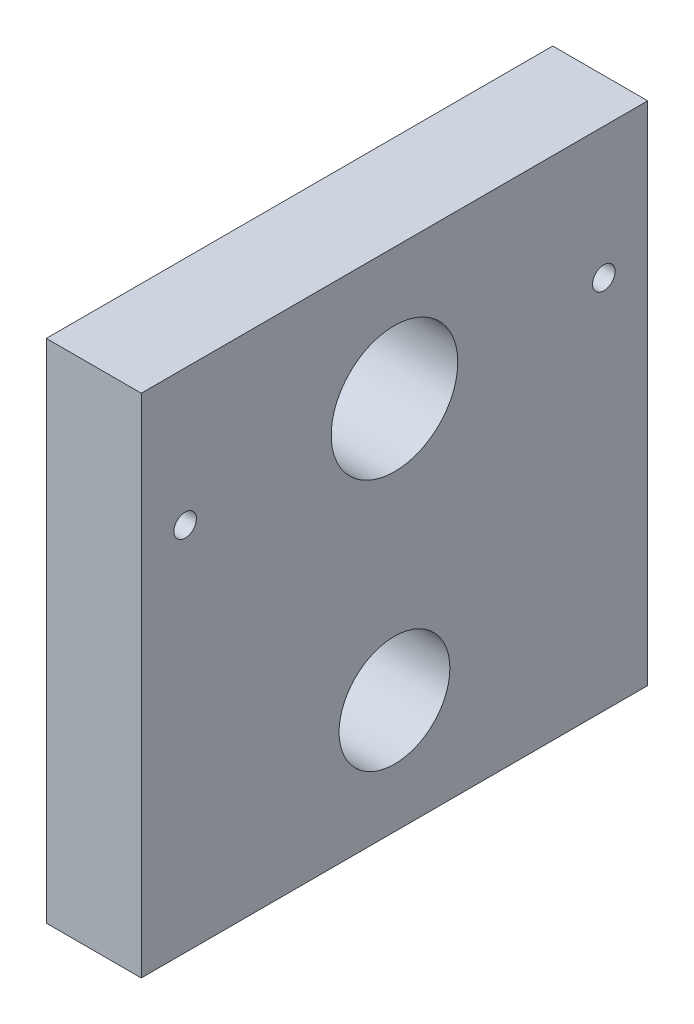
SolidWorks part; units mm, degrees
ref_plane "Front Plane" through (0, 0, 0) normal (0, 0, 1) x (1, 0, 0)
ref_plane "Top Plane" through (0, 0, 0) normal (0, 1, 0) x (1, 0, 0)
ref_plane "Right Plane" through (0, 0, 0) normal (1, 0, 0) x (0, 0, -1)
sketch "Sketch1" plane through (0, 0, 0) normal (1, 0, 0) x (0, 0, -1)
  line L1 (-25.4, -25.4) -> (25.4, -25.4)
  line L2 (-25.4, -25.4) -> (-25.4, 25.4)
  line L3 (-25.4, 25.4) -> (25.4, 25.4)
  line L4 (25.4, -25.4) -> (25.4, 25.4)
  line L5 (-25.4, -25.4) -> (25.4, 25.4) construction
  line L6 (-25.4, 25.4) -> (25.4, -25.4) construction
  point P0 (0, 0)
  dimension "D1" = 50.8
  dimension "D2" = 50.8
extrude "Boss-Extrude1" add sketch "Sketch1" along normal blind 9.525
hole_wizard "7/16 (0.4375) Diameter Hole1" positions "Sketch9" profile "Sketch8" hole size "7/16" standard "ANSI Inch"
sketch "Sketch9" plane through (9.525, 0, 0) normal (1, 0, 0) x (0, 0, -1)
  line L0 (-25.4, -25.4) -> (25.4, -25.4) construction
  point P0 (0, -13.97)
  dimension "D1" = 11.43
sketch "Sketch8" plane through (9.525, -13.97, 0) normal (0, 1, 0) x (0, 0, -1)
  line L0 (0, 0) -> (0, 73.4425)
  line L1 (0, 73.4425) -> (5.5562, 70.104)
  line L2 (5.5562, 70.104) -> (5.5562, 0)
  line L5 (5.5562, 0) -> (0, 0)
  line L10 (0, 73.4425) -> (-5.5563, 70.104) construction
  line L11 (0, -6.35) -> (0, 107.95) construction
  dimension "Hole Dia." = 11.1125
  dimension "Hole Depth" = 70.104
  dimension "Drill Angle" = 118
hole_wizard "1/2 (0.5) Diameter Hole2" positions "Sketch3" profile "Sketch2" hole size "1/2" standard "ANSI Inch"
sketch "Sketch3" plane through (9.525, 0, 0) normal (1, 0, 0) x (0, 0, -1)
  circle A0 centre (0, -13.97) radius 5.5562 construction
  point P0 (0, 12.2301)
  dimension "D1" = 26.2001
  dimension "D2" = 0
sketch "Sketch2" plane through (9.525, 12.2301, 0) normal (0, 1, 0) x (0, 0, -1)
  line L0 (0, 0) -> (0, 73.9195)
  line L1 (0, 73.9195) -> (6.35, 70.104)
  line L2 (6.35, 70.104) -> (6.35, 0)
  line L5 (6.35, 0) -> (0, 0)
  line L10 (0, 73.9195) -> (-6.35, 70.104) construction
  line L11 (0, -6.35) -> (0, 107.95) construction
  dimension "Hole Dia." = 12.7
  dimension "Hole Depth" = 70.104
  dimension "Drill Angle" = 118
hole_wizard "#4-40 Tapped Hole1" positions "Sketch5" profile "Sketch4" tap size "#4-40" standard "ANSI Inch" end condition through all
sketch "Sketch5" plane through (9.525, 0, 0) normal (1, 0, 0) x (0, 0, -1)
  circle A0 centre (0, 12.2301) radius 6.35 construction
  point P0 (21, 12.2301)
  point P2 (-21, 11.7415)
  dimension "D1" = 0.4886
  dimension "D2" = 0
  dimension "D3" = 21
  dimension "D4" = 42
sketch "Sketch4" plane through (9.525, 12.2301, -21) normal (0, 1, 0) x (0, 0, -1)
  line L0 (0, 0) -> (0, 9.525)
  line L1 (0, 9.525) -> (1.1303, 9.525)
  line L2 (1.1303, 9.525) -> (1.1303, 0)
  line L5 (1.1303, 0) -> (0, 0)
  line L11 (0, -6.35) -> (0, 107.95) construction
  dimension "Thread Major Dia." = 2.2606
  dimension "Thru Tap Drill Depth" = 9.525
hole_wizard "#10-32 Tapped Hole1" positions "Sketch11" profile "Sketch10" tap size "#10-32" standard "ANSI Inch"
sketch "Sketch11" plane through (-0.6693, 7.9801, -25.4) normal (0, 0, -1) x (-1, 0, 0)
  line L0 (-10.1943, 17.4199) -> (-0.6693, 17.4199) construction
  line L2 (-10.1943, -33.3801) -> (-0.6693, -33.3801) construction
  line L3 (-10.1943, 17.4199) -> (-0.6693, 17.4199) construction
  point P0 (-5.4318, -27.0301)
  point P2 (-5.4318, 11.0699)
  point P6 (-5.4318, 17.4199)
  dimension "D1" = 0
  dimension "D2" = 0
  dimension "D3" = 6.35
  dimension "D4" = 6.35
sketch "Sketch10" plane through (4.7625, -19.05, -25.4) normal (1, 0, 0) x (0, 1, 0)
  line L0 (0, 0) -> (0, 13.1513)
  line L1 (0, 13.1513) -> (2.0193, 11.938)
  line L2 (2.0193, 11.938) -> (2.0193, 0)
  line L5 (2.0193, 0) -> (0, 0)
  line L10 (0, 13.1513) -> (-2.0193, 11.938) construction
  line L11 (0, -6.35) -> (0, 107.95) construction
  dimension "Tap Drill Dia." = 4.0386
  dimension "Tap Drill Depth" = 11.938
  dimension "Drill Angle" = 118
cosmetic thread "Hole Thread1" parameters "D1"=9.652, "D2"=4.826
cosmetic thread "Hole Thread2" parameters "D1"=9.652, "D2"=4.826
